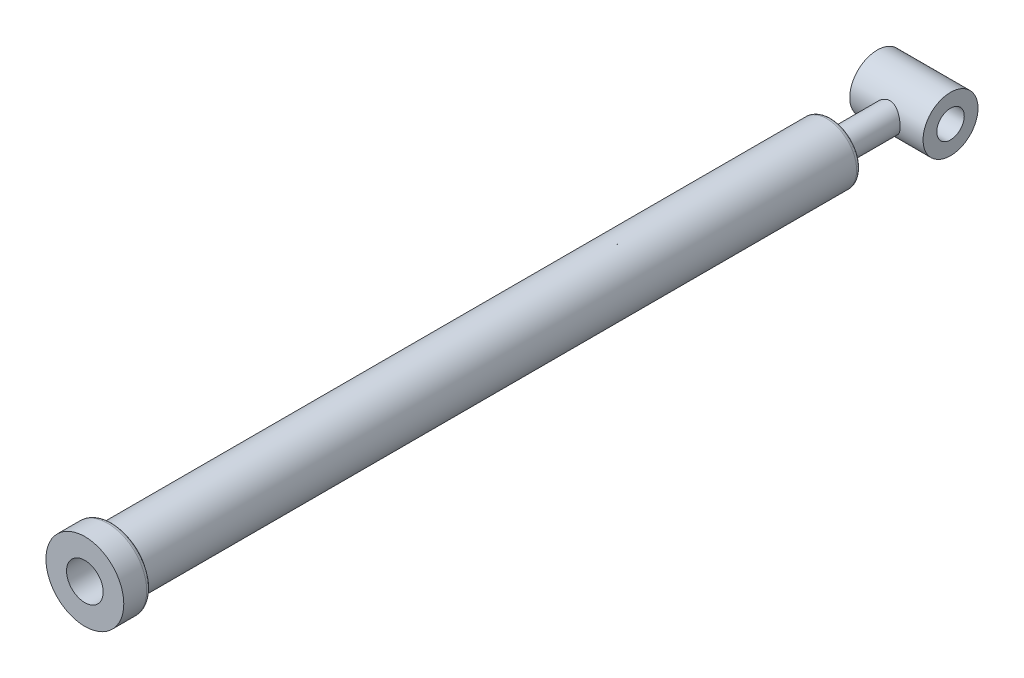
SolidWorks part; units mm, degrees
ref_plane "Front Plane" through (0, 0, 0) normal (0, 0, 1) x (1, 0, 0)
ref_plane "Top Plane" through (0, 0, 0) normal (0, 1, 0) x (1, 0, 0)
ref_plane "Right Plane" through (0, 0, 0) normal (1, 0, 0) x (0, 0, -1)
sketch "Sketch1" plane through (0, 0, 0) normal (0, 0, 1) x (1, 0, 0)
  circle A0 centre (0, 0) radius 20
  circle A1 centre (0, 0) radius 42.5
  dimension "D1" = 85
  dimension "D2" = 40
extrude "Boss-Extrude1" add sketch "Sketch1" against normal blind 30
sketch "Sketch2" plane through (0, 0, -30) normal (0, 0, -1) x (-1, 0, 0)
  circle A0 centre (0, 0) radius 32.5
  circle A1 centre (0, 0) radius 20 construction
  circle A2 centre (0, 0) radius 20
  dimension "D1" = 65
extrude "Boss-Extrude2" add sketch "Sketch2" along normal blind 780
sketch "Sketch3" plane through (0, 0, -810) normal (0, 0, -1) x (-1, 0, 0)
  circle A1 centre (0, 0) radius 32.5
  circle A2 centre (0, 0) radius 32.5
  dimension "D1" = 0
extrude "Boss-Extrude3" add sketch "Sketch3" along normal blind 5
sketch "Sketch4" plane through (0, 0, -815) normal (0, 0, -1) x (-1, 0, 0)
  circle A0 centre (0, 0) radius 15
  dimension "D1" = 30
extrude "Boss-Extrude4" add sketch "Sketch4" along normal blind 65
sketch "Sketch5" plane through (0, 0, 0) normal (1, 0, 0) x (0, 0, -1)
  line L0 (815, -32.5) -> (815, 32.5) construction
  line L1 (880, 0) -> (905, 0) construction
  line L2 (880, -15) -> (880, 15) construction
  circle A0 centre (905, 0) radius 30
  circle A1 centre (905, 0) radius 15
  dimension "D2" = 60
  dimension "D3" = 30
  dimension "D1" = 90
extrude "Boss-Extrude5" add sketch "Sketch5" along normal mid plane 80
fillet "Fillet1" radius 5 4 edges at (-32.5, 0, -815) (-15, 0, -815) (32.5, 0, -30) (42.5, 0, -30)
